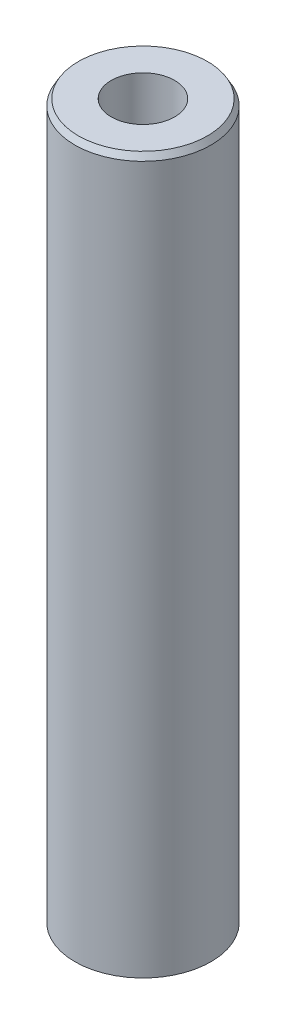
SolidWorks part; units mm, degrees
ref_plane "Front Plane" through (0, 0, 0) normal (0, 0, 1) x (1, 0, 0)
ref_plane "Top Plane" through (0, 0, 0) normal (0, 1, 0) x (1, 0, 0)
ref_plane "Right Plane" through (0, 0, 0) normal (1, 0, 0) x (0, 0, -1)
sketch "Sketch1" plane through (0, 0, 0) normal (0, 1, 0) x (1, 0, 0)
  circle A0 centre (0, 0) radius 10
  dimension "SHAFT_OD" = 20
extrude "Boss-Extrude1" add sketch "Sketch1" along normal blind 105.3357
sketch "Sketch2" plane through (0, 0, 0) normal (0, 1, 0) x (1, 0, 0)
  circle A0 centre (0, 0) radius 4.656
  dimension "BORE_D" = 9.3121
extrude "Cut-Extrude1" cut sketch "Sketch2" along normal through all
chamfer "Chamfer1" distance 0.9063 angle 30 2 edges at (0, 105.3357, 10) (0, 0, 10) first distance on face at (0, 105.3357, 10) first distance on face at (0, 0, 4.656)
